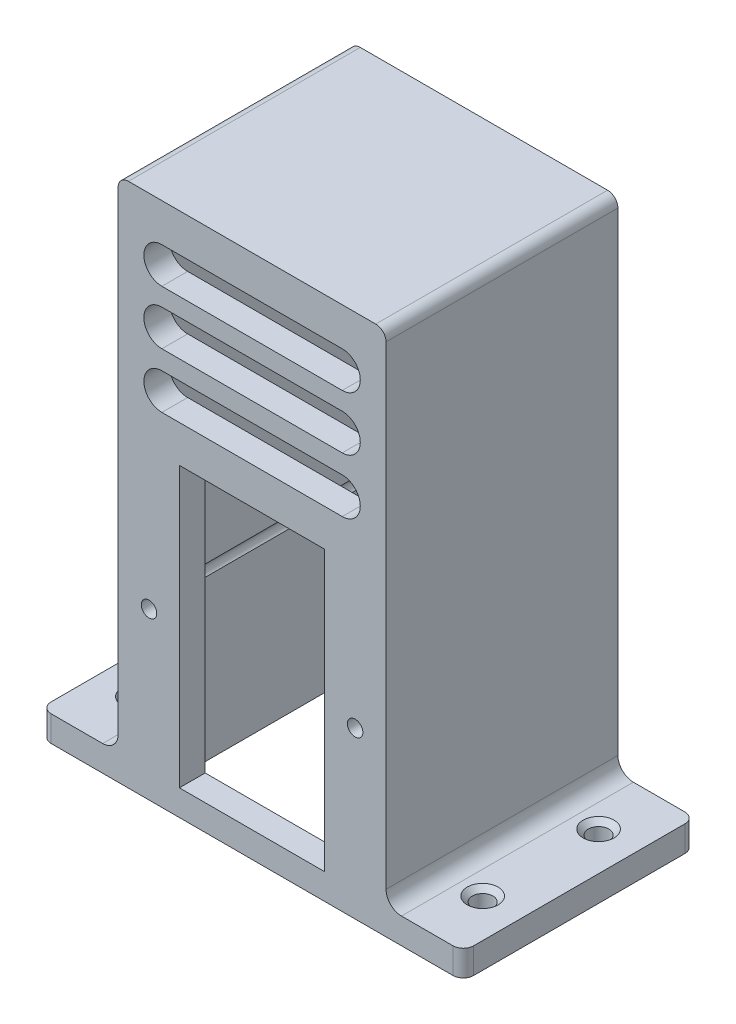
SolidWorks part; units mm, degrees
material "ABS"
ref_plane "Plano frontal" through (0, 0, 0) normal (0, 0, 1) x (1, 0, 0)
ref_plane "Plano superior" through (0, 0, 0) normal (0, 1, 0) x (1, 0, 0)
ref_plane "Plano direito" through (0, 0, 0) normal (1, 0, 0) x (0, 0, -1)
sketch "Esboço7" plane through (0, 0, 0) normal (0, 1, 0) x (1, 0, 0)
  line L0 (-21, 0) -> (21, 0)
  line L1 (21, 0) -> (26, 0)
  line L2 (-21, 0) -> (-26, 0)
  line L3 (26, 0) -> (41, 0)
  line L4 (-26, 0) -> (-41, 0)
  line L5 (-41, 0) -> (-41, 5)
  line L6 (-41, 5) -> (-41, 45)
  line L7 (41, 0) -> (41, 5)
  line L8 (41, 5) -> (41, 45)
  line L9 (-41, 45) -> (41, 45)
  line L10 (-41, 5) -> (41, 5) construction
  line L11 (-21, 5) -> (-21, 45)
  line L12 (-21, 5) -> (21, 5)
  line L13 (21, 5) -> (21, 45)
  line L14 (-26, 0) -> (-26, 45)
  line L15 (26, 0) -> (26, 45)
  point P4 (0, 0)
  dimension "D1" = 42
  dimension "D2" = 5
  dimension "D3" = 42
  dimension "D5" = 15
  dimension "D7" = 40
extrude "Ressalto-extrusão4" add sketch "Esboço7" along normal blind 5 contours L6 L10 L14 L9 | L14 L10 L11 L9 | L10 L5 L4 L14 | L10 L15 L3 L7 | L15 L10 L8 L9 | L13 L10 L15 L9 | L10 L14 L2 L0 L1 L15 L12 region at (0, 0, -2.5) region at (-33.5, 0, -2.5) region at (33.5, 0, -2.5) region at (-23.5, 0, -25) region at (-33.5, 0, -25) region at (33.5, 0, -25) region at (23.5, 0, -25)
sketch "Esboço8" plane through (0, 0, 0) normal (0, 1, 0) x (1, 0, 0)
  line L0 (-21, 45) -> (-26, 45)
  line L1 (-41, 45) -> (-21, 45) construction
  line L2 (-26, 45) -> (-26, 0)
  line L3 (41, 0) -> (-41, 0) construction
  line L4 (-26, 0) -> (26, 0)
  line L5 (26, 0) -> (26, 45)
  line L6 (21, 45) -> (41, 45) construction
  line L7 (26, 45) -> (21, 45)
  line L8 (21, 5) -> (21, 45) construction
  line L9 (21, 45) -> (21, 5)
  line L10 (21, 5) -> (-21, 5)
  line L11 (-21, 5) -> (-21, 45)
  dimension "D1" = 5
extrude "Ressalto-extrusão6" add sketch "Esboço8" along normal blind 102
sketch "Esboço9" plane through (0, 0, 0) normal (0, 0, 1) x (1, 0, 0)
  line L0 (-26, 102) -> (-26, 97)
  line L1 (-26, 102) -> (-26, 5) construction
  line L2 (-26, 97) -> (26, 97)
  line L3 (26, 102) -> (26, 5) construction
  line L4 (26, 97) -> (26, 102)
  line L5 (-26, 102) -> (26, 102) construction
  line L6 (26, 102) -> (-26, 102)
  dimension "D1" = 5
extrude "Ressalto-extrusão7" add sketch "Esboço9" against normal blind 45
sketch "Esboço10" plane through (0, 0, 0) normal (0, 1, 0) x (1, 0, 0)
  circle A0 centre (-33.5, 33.75) radius 2
  circle A1 centre (-33.5, 11.25) radius 2
  circle A2 centre (33.5, 11.25) radius 2
  circle A3 centre (33.5, 33.75) radius 2
  dimension "D1" = 4
extrude "Corte-extrusão1" cut sketch "Esboço10" along normal through all
fillet "Filete1" radius 3 1 edges at (26, 5, -22.5)
fillet "Filete2" radius 3 1 edges at (-26, 5, -22.5)
fillet "Filete3" radius 2 4 edges at (41, 2.5, 0) (41, 2.5, -45) (-41, 2.5, 0) (-41, 2.5, -45)
fillet "Filete5" radius 2 1 edges at (26, 102, -22.5)
fillet "Filete6" radius 2 1 edges at (-26, 102, -22.5)
sketch "Esboço11" plane through (0, 0, 0) normal (0, 0, 1) x (1, 0, 0)
  line L0 (39, 0) -> (-39, 0) construction
  line L1 (-26, 100) -> (-26, 8) construction
  line L4 (-14.1, 5) -> (14.1, 5)
  line L5 (14.1, 5) -> (14.1, 59.2)
  line L6 (14.1, 59.2) -> (-14.1, 59.2)
  line L7 (-14.1, 59.2) -> (-14.1, 5)
  circle A0 centre (20, 32.1) radius 1.5
  circle A1 centre (-20, 32.1) radius 1.5
  point P5 (0, 5)
  point P13 (0, 5)
  point P14 (14.1, 32.1)
  dimension "D6" = 3
  dimension "D4" = 5.9
  dimension "D1" = 5
  dimension "D2" = 28.2
  dimension "D3" = 54.2
  dimension "D5" = 40
  dimension "D7" = 11.9
extrude "Corte-extrusão2" cut sketch "Esboço11" against normal through all
sketch "Esboço12" plane through (0, 0, 0) normal (0, 0, 1) x (1, 0, 0)
  line L0 (-17.5, 91.0956) -> (17.5, 91.0956) construction
  line L1 (0, 102) -> (0, 59.2) construction
  line L2 (-24, 102) -> (24, 102) construction
  line L3 (14.1, 59.2) -> (-14.1, 59.2) construction
  line L5 (-17.5, 94.5956) -> (17.5, 94.5956)
  line L6 (0, 91.0956) -> (11.6878, 91.0956) construction
  line L8 (-17.5, 87.5956) -> (17.5, 87.5956)
  line L9 (0, 69.9) -> (17.5, 69.9) construction
  line L10 (-17.5, 80.6) -> (17.5, 80.6) construction
  line L11 (-17.5, 84.1) -> (17.5, 84.1)
  line L12 (-17.5, 77.1) -> (17.5, 77.1)
  line L13 (-17.5, 69.9) -> (17.5, 69.9) construction
  line L14 (-17.5, 73.4) -> (17.5, 73.4)
  line L15 (-17.5, 66.4) -> (17.5, 66.4)
  arc A0 (-17.5, 94.5956) -> (-17.5, 87.5956) centre (-17.5, 91.0956) ccw
  arc A1 (17.5, 87.5956) -> (17.5, 94.5956) centre (17.5, 91.0956) ccw
  arc A2 (-17.5, 84.1) -> (-17.5, 77.1) centre (-17.5, 80.6) ccw
  arc A3 (17.5, 77.1) -> (17.5, 84.1) centre (17.5, 80.6) ccw
  arc A4 (-17.5, 73.4) -> (-17.5, 66.4) centre (-17.5, 69.9) ccw
  arc A5 (17.5, 66.4) -> (17.5, 73.4) centre (17.5, 69.9) ccw
  point P2 (0, 91.0956)
  point P6 (0, 80.6)
  point P16 (0, 80.6)
  point P23 (0, 69.9)
  dimension "D1" = 3.5
  dimension "D4" = 0
  dimension "D2" = 35
  dimension "D3" = 0
  dimension "D5" = 0
extrude "Corte-extrusão3" cut sketch "Esboço12" against normal through all
chamfer "Chanfro1" distance 1 angle 45 2 edges at (33.5, 5, -9.25) (33.5, 5, -31.75)
chamfer "Chanfro2" distance 1 angle 45 2 edges at (-33.5, 5, -31.75) (-33.5, 5, -9.25)
